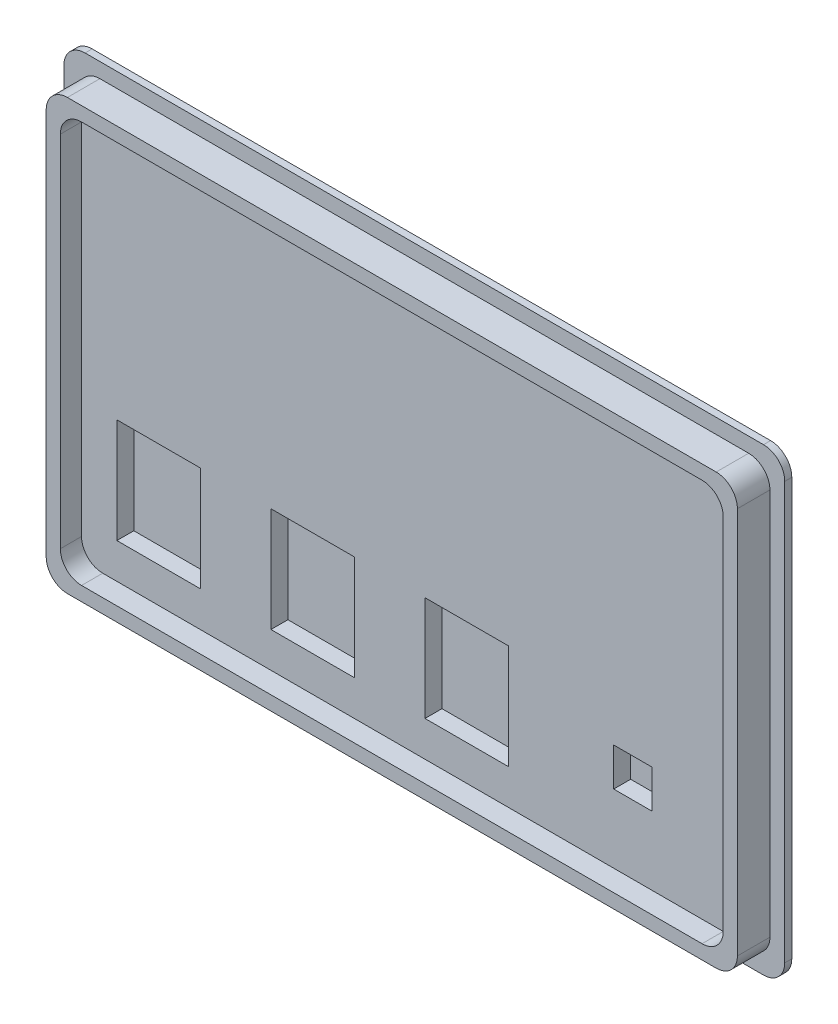
SolidWorks part; units mm, degrees
note: The reader was unsure of these and kept them because the rebuilt part matched: shared geometry of "Skica1<3>", "Skica1<5>", "Skica1<6>".
ref_plane "Přední rovina" through (0, 0, 0) normal (0, 0, 1) x (1, 0, 0)
ref_plane "Horní rovina" through (0, 0, 0) normal (0, 1, 0) x (1, 0, 0)
ref_plane "Pravá rovina" through (0, 0, 0) normal (1, 0, 0) x (0, 0, -1)
sketch "Skica1" plane through (0, 0, 0) normal (0, 0, 1) x (1, 0, 0)
  line L0 (64.5, 16.5) -> (52.7, 16.5) construction
  line L1 (0, 0) -> (102, 0)
  line L2 (0, 0) -> (0, 65)
  line L3 (0, 65) -> (102, 65)
  line L4 (102, 0) -> (102, 65)
  line L45 (2.1, 62.9) -> (99.9, 62.9)
  line L46 (2.1, 62.9) -> (2.1, 2.1)
  line L47 (2.1, 2.1) -> (99.9, 2.1)
  line L48 (99.9, 62.9) -> (99.9, 2.1)
  line L49 (9.1, 23.9) -> (20.9, 23.9)
  line L50 (9.1, 23.9) -> (9.1, 9.1)
  line L51 (9.1, 9.1) -> (20.9, 9.1)
  line L52 (20.9, 23.9) -> (20.9, 9.1)
  line L53 (30.9, 23.9) -> (42.7, 23.9)
  line L54 (30.9, 23.9) -> (30.9, 9.1)
  line L55 (30.9, 9.1) -> (42.7, 9.1)
  line L56 (42.7, 23.9) -> (42.7, 9.1)
  line L57 (52.7, 23.9) -> (64.5, 23.9)
  line L58 (52.7, 23.9) -> (52.7, 9.1)
  line L59 (52.7, 9.1) -> (64.5, 9.1)
  line L60 (64.5, 23.9) -> (64.5, 9.1)
  line L62 (4.1, 60.9) -> (97.9, 60.9)
  line L63 (79.4, 13.8) -> (84.8, 13.8)
  line L64 (4.1, 60.9) -> (4.1, 4.1)
  line L65 (79.4, 13.8) -> (79.4, 19.2)
  line L66 (79.4, 19.2) -> (84.8, 19.2)
  line L67 (84.8, 13.8) -> (84.8, 19.2)
  line L68 (4.1, 4.1) -> (97.9, 4.1)
  line L69 (97.9, 60.9) -> (97.9, 4.1)
  dimension "D4" = 14.9
  dimension "D5" = 2
  dimension "D6" = 2
  dimension "D7" = 2
  dimension "D8" = 2
  dimension "D15" = 102
  dimension "D18" = 65
  dimension "D20" = 2.1
  dimension "D21" = 2.1
  dimension "D22" = 2.1
  dimension "D23" = 2.1
  dimension "D25" = 11.8
  dimension "D26" = 14.8
  dimension "D27" = 11.8
  dimension "D28" = 11.8
  dimension "D32" = 7
  dimension "D33" = 7
  dimension "D34" = 10
  dimension "D35" = 10
  dimension "D36" = 5.4
  dimension "D37" = 5.4
  dimension "D39" = 97.8
extrude "Přidat vysunutím1" add sketch "Skica1" along normal blind 2.6
extrude "Přidat vysunutím2" add sketch "Skica1<3>" along normal blind 1 contours L1 L4 L3 L2 L45 L48 L47 L46
sketch "Skica1<3>" plane through (0, 0, 0) normal (0, 0, 1) x (1, 0, 0) same geometry as "Skica1"
extrude "Přidat vysunutím3" add sketch "Skica1<5>" along normal blind 0.2
sketch "Skica1<5>" plane through (0, 0, 0) normal (0, 0, 1) x (1, 0, 0) same geometry as "Skica1"
fillet "Zaoblit1" radius 3 4 edges at (102, 65, 0.5) (0, 65, 0.5) (0, 0, 0.5) (102, 0, 0.5)
fillet "Zaoblit2" radius 3 4 edges at (2.1, 2.1, 1.8) (2.1, 62.9, 1.8) (99.9, 62.9, 1.8) (99.9, 2.1, 1.8)
extrude "Přidat vysunutím4" add sketch "Skica1<6>" along normal blind 5.6 contours L48 L45 L46 L47 L62 L69 L68 L64
sketch "Skica1<6>" plane through (0, 0, 0) normal (0, 0, 1) x (1, 0, 0) same geometry as "Skica1"
fillet "Zaoblit4" radius 3 4 edges at (2.1, 2.1, 3.3) (99.9, 2.1, 3.3) (99.9, 62.9, 3.3) (2.1, 62.9, 3.3)
fillet "Zaoblit5" radius 3 4 edges at (4.1, 4.1, 4.1) (97.9, 4.1, 4.1) (97.9, 60.9, 4.1) (4.1, 60.9, 4.1)
